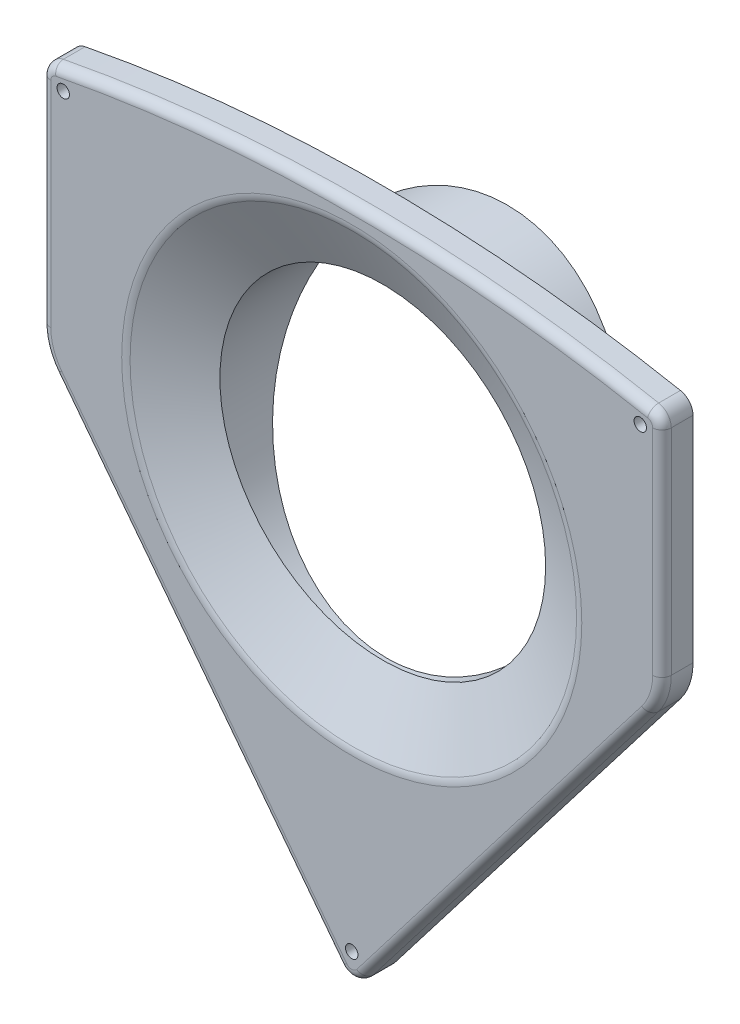
SolidWorks part; units mm, degrees
ref_plane "Front Plane" through (0, 0, 0) normal (0, 0, 1) x (1, 0, 0)
ref_plane "Top Plane" through (0, 0, 0) normal (0, 1, 0) x (1, 0, 0)
ref_plane "Right Plane" through (0, 0, 0) normal (1, 0, 0) x (0, 0, -1)
sketch "Sketch1" plane through (0, 0, 0) normal (0, 0, 1) x (1, 0, 0)
  line L0 (0, 109.2779) -> (0, -140.5615) construction
  line L1 (100, 99.2779) -> (100, 19.2779)
  line L2 (100, 19.2779) -> (0, -110.7221)
  line L3 (-100, 19.2779) -> (0, -110.7221)
  line L4 (-100, 99.2779) -> (-100, 19.2779)
  arc A0 (-100, 99.2779) -> (100, 99.2779) centre (0, -395.7221) cw
  point P5 (100, 59.2779)
  dimension "D8" = 505
  dimension "D1" = 80
  dimension "D2" = 130
  dimension "D3" = 100
  dimension "D4" = 80
  dimension "D5" = 130
  dimension "D6" = 100
  dimension "D7" = 10
  dimension "D9" = 37.569
  dimension "D10" = 37.569
  dimension "D11" = 249.8393
  dimension "D12" = 100
extrude "Boss-Extrude1" add sketch "Sketch1" along normal blind 10
sketch "Sketch2" plane through (0, 0, 0) normal (0, 0, 1) x (1, 0, 0)
  line L0 (0, 193.1871) -> (0, -208.8274) construction
  circle A0 centre (0, 29.2779) radius 52.5
  dimension "D1" = 105
  dimension "D2" = 70
  dimension "D3" = 29.2779
sketch "Sketch3" plane through (0, 0, 10) normal (0, 0, 1) x (1, 0, 0)
  circle A0 centre (0, 29.2779) radius 73
  dimension "D1" = 146
  dimension "D2" = 70
loft "Cut-Loft1" cut profiles "Sketch3", "Sketch2" connector at (-67.7719, 56.4066, 10) connector at (-47.1813, 52.3034, 0)
fillet "Fillet3" radius 5 1 edges at (0, -110.7221, 5)
fillet "Fillet4" radius 20 2 edges at (100, 19.2779, 5) (-100, 19.2779, 5)
shell "Shell4" thickness 2 removed face at (52.5, 29.2779, 0)
sketch "Sketch12" plane through (0, 0, 8) normal (0, 0, -1) x (-1, 0, 0)
  line L0 (-9.1695, -95.5215) -> (9.1695, -95.5215)
  line L4 (-94.2672, 15.1055) -> (-2.3779, -104.3507)
  line L5 (2.3779, -104.3507) -> (94.2672, 15.1055)
  line L6 (98, 26.0803) -> (98, 97.6388)
  line L7 (-98, 97.6388) -> (-98, 26.0803)
  line L8 (-9.1695, -95.5215) -> (-2.3779, -104.3507)
  line L9 (2.3779, -104.3507) -> (9.1695, -95.5215)
  line L10 (98, 87.6388) -> (98, 97.6388)
  line L11 (-98, 97.6388) -> (-98, 87.6388)
  arc A0 (-98, 87.6388) -> (-88.1727, 99.4895) centre (-98, 97.6388) ccw
  arc A1 (88.1727, 99.4895) -> (98, 87.6388) centre (98, 97.6388) ccw
  arc A2 (-88.1727, 99.4895) -> (-98, 97.6388) centre (0, -395.7221) ccw
  arc A4 (-2.3779, -104.3507) -> (2.3779, -104.3507) centre (0, -102.5215) ccw
  arc A5 (94.2672, 15.1055) -> (98, 26.0803) centre (80, 26.0803) ccw
  arc A6 (98, 97.6388) -> (-98, 97.6388) centre (0, -395.7221) ccw
  arc A7 (-98, 26.0803) -> (-94.2672, 15.1055) centre (-80, 26.0803) ccw
  arc A8 (-2.3779, -104.3507) -> (2.3779, -104.3507) centre (0, -102.5215) ccw
  arc A10 (98, 97.6388) -> (88.1727, 99.4895) centre (0, -395.7221) ccw
  dimension "D2" = 20
  dimension "D3" = 20
  dimension "D4" = 7
  dimension "D1" = 0
extrude "Boss-Extrude3" add sketch "Sketch12" along normal blind 8
sketch "Sketch16" plane through (0, 0, 8) normal (0, 0, -1) x (-1, 0, 0)
  line L0 (-132.51, 0) -> (173.2387, 0) construction
  line L1 (0, 142.9203) -> (0, -200.5749) construction
  line L2 (9.1695, -95.5215) -> (-9.1695, -95.5215) construction
  line L6 (-98, 26.0803) -> (-98, 87.6388) construction
  line L7 (-98, 26.0803) -> (-98, 87.6388)
  line L8 (98, 87.6388) -> (98, 26.0803) construction
  line L9 (98, 87.6388) -> (98, 26.0803)
  line L10 (-100, 26.0803) -> (-100, 99.2779) construction
  line L11 (100, 99.2779) -> (100, 26.0803) construction
  circle A2 centre (0, -99.5215) radius 2
  circle A7 centre (-93, 94.1388) radius 2
  circle A8 centre (93, 94.1388) radius 2
  dimension "D2" = 4
  dimension "D3" = 4
  dimension "D4" = 4
  dimension "D1" = 4
  dimension "D5" = 7
  dimension "D6" = 6.5
  dimension "D7" = 7
  dimension "D8" = 6.5
extrude "Cut-Extrude8" cut sketch "Sketch16" along normal mid plane 18 contours A7 | A8 | A2
sketch "Sketch5" plane through (0, 0, 0) normal (0, 0, -1) x (-1, 0, 0)
  circle A0 centre (0, 29.2779) radius 52.5 construction
  circle A1 centre (0, 29.2779) radius 52.5
  circle A2 centre (0, 29.2779) radius 54.5
  dimension "D1" = 109
extrude "Boss-Extrude2" add sketch "Sketch5" along normal blind 60
sketch "Sketch6" plane through (0, 0, 0) normal (0, 0, -1) x (-1, 0, 0)
  line L0 (-63.295, -23.2221) -> (55.6239, -23.2221) construction
  circle A0 centre (0, 29.2779) radius 52.5 construction
ref_plane "Plane1" through (0, -4.1476, -8.8946) normal (0, -0.4226, -0.9063) x (-1, 0, 0)
sketch "Sketch7" plane through (0, -4.1476, -8.8946) normal (0, -0.4226, -0.9063) x (-1, 0, 0)
  circle A1 centre (0, 68.9154) radius 91.7744
  ellipse E0 centre (0, 26.5348) end of major axis (54.5, 26.5348) minor radius 49.3938 construction
ref_plane "Plane2" through (0, 0, -0.5) normal (0, 0, 1) x (1, 0, 0)
sketch "Sketch8" plane through (0, 0, -0.5) normal (0, 0, 1) x (1, 0, 0)
  line L0 (102.5717, -25.2221) -> (-109.0805, -25.2221) construction
  circle A0 centre (0, 29.2779) radius 54.5 construction
ref_plane "Plane3" through (0, -4.6963, -10.0713) normal (0, -0.4226, -0.9063) x (-1, 0, 0)
sketch "Sketch9" plane through (0, -4.6963, -10.0713) normal (0, -0.4226, -0.9063) x (-1, 0, 0)
  line L0 (-102.5717, -22.6477) -> (109.0805, -22.6477) construction
  circle A0 centre (0, 89.7194) radius 112.3671
extrude "Cut-Extrude5" cut sketch "Sketch9" along normal blind 60
ref_plane "Plane4" through (0, -4.0305, -9.4953) normal (0, -0.3907, -0.9205) x (-1, 0, 0)
sketch "Sketch10" plane through (0, -4.0305, -9.4953) normal (0, -0.3907, -0.9205) x (-1, 0, 0)
  line L0 (-102.5717, -23.0217) -> (109.0805, -23.0217) construction
  circle A0 centre (0, 68.8917) radius 91.9134
extrude "Cut-Extrude6" cut sketch "Sketch10" along normal blind 10
ref_plane "Plane5" through (0, -3.1111, -8.5477) normal (0, -0.342, -0.9397) x (-1, 0, 0)
sketch "Sketch11" plane through (0, -3.1111, -8.5477) normal (0, -0.342, -0.9397) x (-1, 0, 0)
  line L0 (-102.5717, -23.53) -> (109.0805, -23.53) construction
  circle A0 centre (0, 55.6513) radius 79.1813
extrude "Cut-Extrude7" cut sketch "Sketch11" along normal blind 10
fillet "Fillet5" radius 5 1 edges at (100, 99.2779, 5)
fillet "Fillet6" radius 5 1 edges at (-100, 99.2779, 5)
fillet "Fillet7" radius 3 10 edges at (98.8568, 98.3519, 10) (100, 60.6251, 10) (98.9348, 19.6402, 10) (49.9078, -45.842, 10) (0, -107.5215, 10) (-49.9078, -45.842, 10) (-98.9348, 19.6402, 10) (-100, 60.6251, 10) (-98.8568, 98.3519, 10) (0, 109.2779, 10)
fillet "Fillet8" radius 5 1 edges at (73, 29.2779, 10)
fillet "Fillet9" radius 2 1 edges at (-54.5, 29.2779, 0)
fillet "Fillet10" radius 5 4 edges at (-51.7184, -40.208, 8) (-97.0413, 20.2842, 8) (-98, 56.8595, 8) (0, 107.2779, 8)
